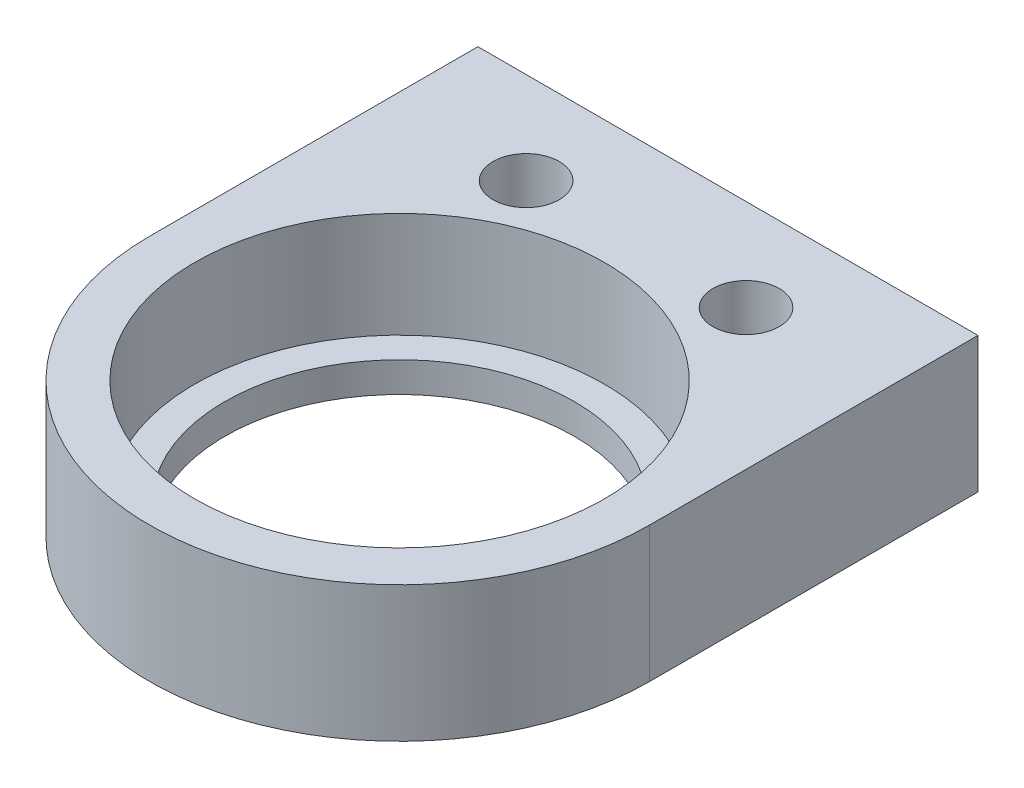
SolidWorks part; units mm, degrees
ref_plane "Front Plane" through (0, 0, 0) normal (0, 0, 1) x (1, 0, 0)
ref_plane "Top Plane" through (0, 0, 0) normal (0, 1, 0) x (1, 0, 0)
ref_plane "Right Plane" through (0, 0, 0) normal (1, 0, 0) x (0, 0, -1)
sketch "Sketch1" plane through (0, 0, 0) normal (0, 1, 0) x (1, 0, 0)
  line L0 (0, 0) -> (14.2506, 0) construction
  line L1 (0, 0) -> (0, 17.6258) construction
  line L3 (-7.366, 0) -> (-7.366, 13.843) construction
  line L4 (-10.541, 0) -> (-10.541, 10.668)
  line L5 (-10.541, 10.668) -> (-20.066, 10.668)
  line L6 (-7.366, 13.843) -> (-20.066, 13.843)
  line L7 (-20.066, 10.668) -> (-20.066, 13.843)
  line L9 (-7.366, 13.843) -> (7.366, 13.843)
  line L11 (10.541, 0) -> (10.541, 10.668)
  line L12 (20.066, 10.668) -> (20.066, 13.843)
  line L13 (7.366, 13.843) -> (20.066, 13.843)
  line L14 (10.541, 10.668) -> (20.066, 10.668)
  line L17 (-7.366, 6.9215) -> (-7.366, 10.668) construction
  line L18 (7.366, 6.9215) -> (7.366, 10.668) construction
  line L19 (-7.366, 10.668) -> (7.366, 10.668) construction
  circle A0 centre (0, 0) radius 6.096
  circle A1 centre (0, 0) radius 10.541 construction
  arc A3 (10.541, 0) -> (-10.541, 0) centre (0, 0) cw
  arc A5 (-7.366, 6.9215) -> (7.366, 6.9215) centre (0, 0) cw construction
  point P18 (0, 13.843)
  point P19 (0, 10.668)
  dimension "D1" = 12.192
  dimension "D2" = 4.445
  dimension "D3" = 13.843
  dimension "D4" = 3.175
  dimension "D5" = 12.7
extrude "Boss-Extrude1" add sketch "Sketch1" along normal blind 4.445
sketch "Sketch5" plane through (0, 0, 0) normal (0, -1, 0) x (1, 0, 0)
  line L0 (-10.541, 0) -> (-10.541, -10.668)
  line L6 (10.541, -10.668) -> (10.541, 0)
  line L7 (-10.541, -10.668) -> (-10.541, -13.843)
  line L9 (20.066, -13.843) -> (-20.066, -13.843) construction
  line L10 (-10.541, -13.843) -> (10.541, -13.843)
  line L12 (10.541, -10.668) -> (10.541, -13.843)
  circle A1 centre (0, 0) radius 6.096 construction
  circle A2 centre (0, 0) radius 9.271 construction
  circle A3 centre (0, 0) radius 7.366
  arc A4 (10.541, 0) -> (-10.541, 0) centre (0, 0) ccw
  dimension "D1" = 14.732
extrude "Boss-Extrude4" add sketch "Sketch5" along normal blind 1.27
sketch "Sketch8" plane through (0, 4.445, 0) normal (0, 1, 0) x (1, 0, 0)
  circle A0 centre (0, 0) radius 8.636
  dimension "D1" = 17.272
extrude "Cut-Extrude4" cut sketch "Sketch8" against normal up to surface (4.445 mm away) up to face at (0, 0, 6.096)
sketch "Sketch6" plane through (0, 4.445, 0) normal (0, 1, 0) x (1, 0, 0)
  line L0 (0, 13.843) -> (0, 9.9695) construction
  line L2 (0, 9.9695) -> (10.541, 9.9695) construction
  line L3 (10.541, 0) -> (10.541, 10.668) construction
  line L4 (20.066, 13.843) -> (-20.066, 13.843) construction
  circle A1 centre (4.6355, 9.9695) radius 1.397
  circle A2 centre (-4.6355, 9.9695) radius 1.397
  point P1 (0, 0)
  dimension "D1" = 2.794
  dimension "D2" = 4.6355
  dimension "D3" = 2.794
extrude "Cut-Extrude2" cut sketch "Sketch6" against normal through all
sketch "Sketch7" plane through (0, 0, -10.668) normal (0, 0, 1) x (1, 0, 0)
  line L1 (10.541, 0) -> (20.066, 0)
  line L2 (10.541, 0) -> (10.541, 4.445)
  line L3 (10.541, 4.445) -> (20.066, 4.445)
  line L4 (20.066, 0) -> (20.066, 4.445)
  line L5 (-10.541, 0) -> (-20.066, 0)
  line L6 (-10.541, 0) -> (-10.541, 4.445)
  line L7 (-10.541, 4.445) -> (-20.066, 4.445)
  line L8 (-20.066, 0) -> (-20.066, 4.445)
extrude "Cut-Extrude3" cut sketch "Sketch7" against normal up to surface (3.175 mm away) up to face at (0, 0.7937, -13.843)
